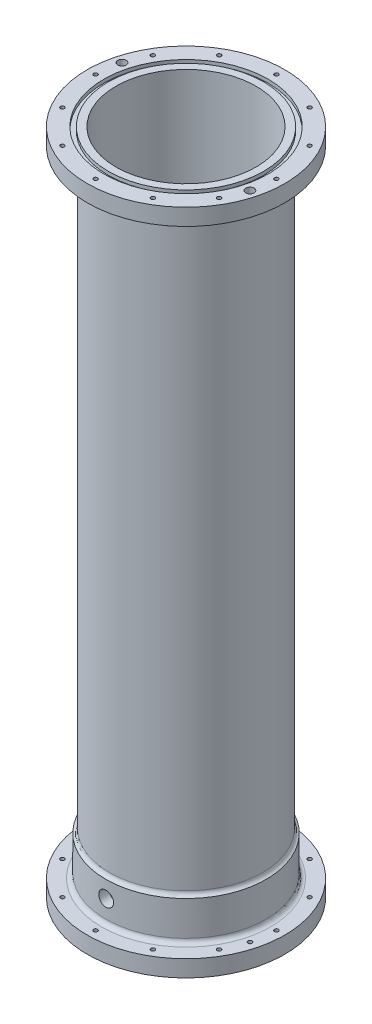
SolidWorks part; units mm, degrees
material "7075-T6 (SN)"
ref_plane "Front Plane" through (0, 0, 0) normal (0, 0, 1) x (1, 0, 0)
ref_plane "Top Plane" through (0, 0, 0) normal (0, 1, 0) x (1, 0, 0)
ref_plane "Right Plane" through (0, 0, 0) normal (1, 0, 0) x (0, 0, -1)
sketch "Sketch2" plane through (0, 0, 0) normal (0, 1, 0) x (1, 0, 0)
  circle A0 centre (0, 0) radius 40
  circle A1 centre (0, 0) radius 43.815
  dimension "D1" = 87.63
  dimension "D2" = 80
extrude "Base Cylinder" add sketch "Sketch2" along normal blind 381
sketch "Sketch3" plane through (0, 0, 0) normal (0, -1, 0) x (1, 0, 0)
  circle A0 centre (0, 0) radius 40
  circle A1 centre (0, 0) radius 56.3562
  dimension "D1" = 112.7125
  dimension "D2" = 80
extrude "Aft Flange" add sketch "Sketch3" against normal blind 9.525
sketch "Sketch6" plane through (0, 0, 0) normal (0, -1, 0) x (1, 0, 0)
  circle A0 centre (0, 0) radius 46.9011
  circle A1 centre (0, 0) radius 44.2849
  dimension "D1" = 93.8022
  dimension "D2" = 88.5698
extrude "Aft O-Ring" cut sketch "Sketch6" against normal blind 1.9812
sketch "Sketch33" plane through (0, 9.525, 0) normal (0, 1, 0) x (1, 0, 0)
  circle A0 centre (0, 0) radius 43.815
  circle A1 centre (0, 0) radius 45.72
  dimension "D1" = 87.63
  dimension "D2" = 91.44
extrude "CriticalBoss" add sketch "Sketch33" along normal blind 22.225
fillet "Fillet1" radius 2.54 2 edges at (0, 9.525, -45.72) (0, 31.75, 43.815)
sketch "Sketch For Bolt Holes" plane through (0, 0, 0) normal (0, -1, 0) x (1, 0, 0)
  circle A0 centre (-51.6255, 0) radius 1.5875
  circle A1 centre (-44.709, 25.8128) radius 1.5875
  circle A2 centre (-25.8128, 44.709) radius 1.5875
  circle A3 centre (0, 51.6255) radius 1.5875
  circle A4 centre (25.8127, 44.709) radius 1.5875
  circle A5 centre (44.709, 25.8128) radius 1.5875
  circle A6 centre (51.6255, 0) radius 1.5875
  circle A7 centre (44.709, -25.8127) radius 1.5875
  circle A8 centre (25.8128, -44.709) radius 1.5875
  circle A9 centre (0, -51.6255) radius 1.5875
  circle A10 centre (-25.8127, -44.709) radius 1.5875
  circle A11 centre (-44.709, -25.8128) radius 1.5875
  point P36 (0, 0)
  dimension "D2" = 3.175
  dimension "D1" = 51.6255
  dimension "D3" = 12
hole_wizard "Bolt Circle" positions "Sketch8" profile "Sketch9" hole size "#4-40" standard "ANSI Inch" end condition up to next
sketch "Sketch8" plane through (0, 0, 0) normal (0, -1, 0) x (-1, 0, 0)
  point P0 (-25.8127, -44.709)
  point P3 (-44.709, -25.8128)
  point P6 (-51.6255, 0)
  point P9 (-44.709, 25.8127)
  point P12 (-25.8128, 44.709)
  point P15 (0, 51.6255)
  point P18 (25.8127, 44.709)
  point P21 (44.709, 25.8128)
  point P24 (51.6255, 0)
  point P27 (44.709, -25.8128)
  point P30 (25.8128, -44.709)
  point P33 (0, -51.6255)
  point P36 (-25.8127, -44.709)
  point P38 (-44.709, -25.8128)
  point P40 (-51.6255, 0)
sketch "Sketch9" plane through (25.8127, 0, 44.709) normal (1, 0, 0) x (0, 0, -1)
  line L0 (0, 0) -> (0, 381)
  line L1 (0, 381) -> (1.1303, 381)
  line L2 (1.1303, 381) -> (1.1303, 0)
  line L5 (1.1303, 0) -> (0, 0)
  line L11 (0, -6.35) -> (0, 107.95) construction
  dimension "Thru Hole Dia." = 2.2606
  dimension "Thru Hole Depth" = 381
sketch "Dowel Hole Sketch" plane through (0, 0, 0) normal (0, -1, 0) x (1, 0, 0)
  line L0 (0, 0) -> (-51.6255, 0) construction
  line L1 (0, 0) -> (-49.8664, -13.3617) construction
  line L2 (0, 0) -> (0, -51.6255) construction
  line L3 (0, 0) -> (49.8664, 13.3617) construction
  circle A0 centre (0, 0) radius 51.6255
  circle A1 centre (-49.8664, -13.3617) radius 4.6172
  circle A2 centre (49.8664, 13.3617) radius 3.4532
  dimension "D1" = 15
hole_wizard "Hole1" positions "Sketch14" profile "Sketch12" legacy end condition up to next
sketch "Sketch14" plane through (0, 0, 0) normal (0, -1, 0) x (-1, 0, 0)
  point P0 (49.8664, 13.3617)
  point P3 (-49.8664, -13.3617)
sketch "Sketch12" plane through (-49.8664, 0, -13.3617) normal (1, 0, 0) x (0, 0, -1)
  line L0 (0, 0) -> (0, 381)
  line L1 (0, 381) -> (1.1906, 381)
  line L2 (1.1906, 381) -> (1.1906, 4.7625)
  line L3 (1.1906, 4.7625) -> (2.3813, 4.7625)
  line L4 (2.3813, 4.7625) -> (2.3813, 0)
  line L5 (2.3813, 0) -> (0, 0)
  line L6 (0, 110) -> (0, -10) construction
  dimension "Diameter" = 2.3813
  dimension "Depth" = 381
  dimension "C-Bore Diameter" = 4.7625
  dimension "C-Bore Depth" = 4.7625
ref_plane "Hoop Mid-Plane" through (0, 190.5, 0) normal (0, 1, 0) x (1, 0, 0)
ref_plane "PressureTapHolePlane" through (0, 0, 45.72) normal (0, 0, 1) x (1, 0, 0)
ref_plane "TemperatureTapPlane" through (0, 0, -45.72) normal (0, 0, 1) x (1, 0, 0)
sketch "ThermoHole" plane through (0, 0, -45.72) normal (0, 0, 1) x (1, 0, 0)
  line L0 (-56.3562, 0) -> (56.3562, 0) construction
  circle A0 centre (0, 22.225) radius 3.175
  dimension "D1" = 22.225
  dimension "D2" = 6.35
hole_wizard "1/8 NPT Tapped ThermocoupleHole" positions "Sketch43" profile "Sketch44" size "1/8" standard "ANSI Inch"
sketch "Sketch43" plane through (0, 0, -45.72) normal (0, 0, 1) x (1, 0, 0)
  line L0 (-56.3562, 0) -> (56.3562, 0) construction
  point P0 (0, 22.225)
  dimension "D1" = 22.225
sketch "Sketch44" plane through (0, 22.225, -45.72) normal (1, 0, 0) x (0, 1, 0)
  line L0 (0, 0) -> (0, 14.2175)
  line L1 (4.2164, 11.684) -> (0, 14.2175)
  line L2 (-4.2164, 11.684) -> (0, 14.2175) construction
  line L3 (4.2164, 11.684) -> (4.2164, 6.858)
  line L4 (4.2164, 6.858) -> (4.9362, 6.858)
  line L5 (4.9362, 6.858) -> (5.1415, 0)
  line L6 (-4.9362, 6.858) -> (-5.1415, 0) construction
  line L7 (5.1415, 0) -> (0, 0)
  line L8 (0, -6.35) -> (0, 107.95) construction
  line L11 (-4.2164, 6.858) -> (-4.9362, 6.858) construction
  dimension "Tap Drill Dia." = 8.4328
  dimension "Tap Drill Depth" = 11.684
  dimension "Thread Dia." = 10.283
  dimension "Thread Angle" = 3.43
  dimension "Thread Depth" = 6.858
  dimension "Drill Angle" = 118
hole_wizard "3/8-24 Tapped Hole1" positions "Sketch48" profile "Sketch49" tap size "3/8-24" standard "ANSI Inch" end condition up to next
sketch "Sketch48" plane through (0, 0, 45.72) normal (0, 0, 1) x (1, 0, 0)
  line L0 (-56.3562, 0) -> (56.3562, 0) construction
  point P0 (0, 22.225)
  dimension "D1" = 22.225
sketch "Sketch49" plane through (0, 22.225, 45.72) normal (1, 0, 0) x (0, -1, 0)
  line L0 (0, 0) -> (0, 5.72)
  line L1 (0, 5.72) -> (4.2164, 5.72)
  line L2 (4.2164, 5.72) -> (4.2164, 0)
  line L5 (4.2164, 0) -> (0, 0)
  line L11 (0, -6.35) -> (0, 107.95) construction
  dimension "Thru Tap Drill Dia." = 8.4328
  dimension "Thru Tap Drill Depth" = 5.72
cosmetic thread "Hole Thread2" parameters "D2"=9.525
mirror "Mirror1" about plane through (0, 190.5, 0) normal (0, 1, 0) of "Aft Flange", "Aft O-Ring", "Bolt Circle", "Hole1"
fillet "Fillet2" radius 2.54 1 edges at (0, 371.475, 43.815)
